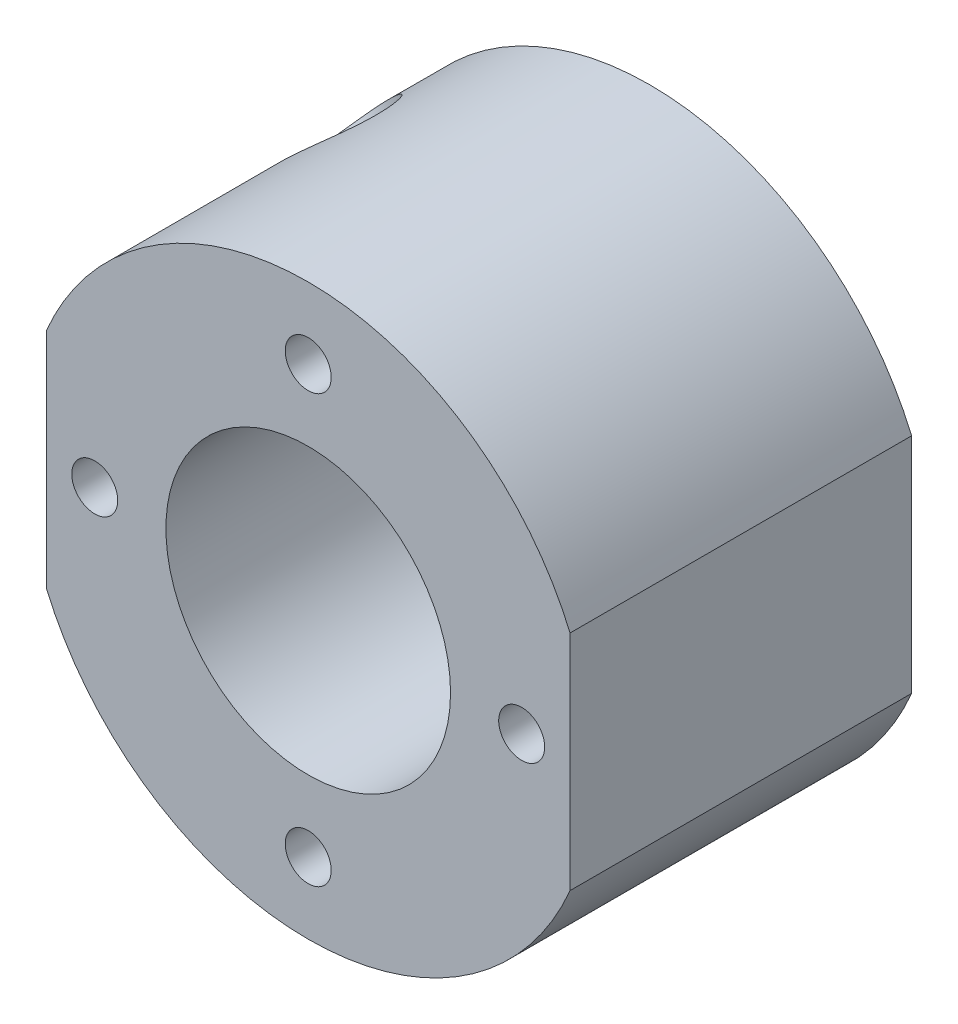
SolidWorks part; units mm, degrees
ref_plane "Front Plane" through (0, 0, 0) normal (0, 0, 1) x (1, 0, 0)
ref_plane "Top Plane" through (0, 0, 0) normal (0, 1, 0) x (1, 0, 0)
ref_plane "Right Plane" through (0, 0, 0) normal (1, 0, 0) x (0, 0, -1)
sketch "Sketch2" plane through (0, 0, 0) normal (0, 0, 1) x (1, 0, 0)
  line L0 (-23, 9.798) -> (-23, -9.798)
  line L1 (23, 9.798) -> (23, -9.798)
  line L2 (-23, 0) -> (23, 0) construction
  arc A0 (-23, -9.798) -> (23, -9.798) centre (0, 0) ccw
  arc A1 (23, 9.798) -> (-23, 9.798) centre (0, 0) ccw
  arc A2 (-23, 9.798) -> (-23, -9.798) centre (0, 0) ccw construction
  arc A3 (23, 9.798) -> (23, -9.798) centre (0, 0) cw construction
  point P10 (0, 0)
  dimension "D1" = 50
  dimension "D2" = 46
extrude "Boss-Extrude1" add sketch "Sketch2" along normal blind 30
sketch "Sketch6" plane through (0, 0, 30) normal (0, 0, 1) x (-1, 0, 0)
  circle A0 centre (0, 0) radius 12.5
  dimension "D1" = 25
extrude "Cut-Extrude1" cut sketch "Sketch6" against normal blind 25
hole_wizard "#10-32 Tapped Hole1" positions "Sketch9" profile "Sketch10" tap size "#10-32" standard "ANSI Inch" end condition through all
sketch "Sketch9" plane through (0, 0, 30) normal (0, 0, 1) x (1, 0, 0)
  line L0 (-18.75, 0) -> (18.75, 0) construction
  line L2 (0, 18.75) -> (0, -18.75) construction
  point P0 (-18.75, 0)
  point P2 (0, 18.75)
  point P4 (18.75, 0)
  point P6 (0, -18.75)
  dimension "D1" = 37.5
sketch "Sketch10" plane through (-18.75, 0, 30) normal (1, 0, 0) x (0, -1, 0)
  line L0 (0, 0) -> (0, 30)
  line L1 (0, 30) -> (2.0193, 30)
  line L2 (2.0193, 30) -> (2.0193, 0)
  line L5 (2.0193, 0) -> (0, 0)
  line L11 (0, -6.35) -> (0, 107.95) construction
  dimension "Thru Tap Drill Dia." = 4.0386
  dimension "Thru Tap Drill Depth" = 30
cosmetic thread "Hole Thread1" parameters "D2"=4.826
cosmetic thread "Hole Thread2" parameters "D2"=4.826
cosmetic thread "Hole Thread3" parameters "D2"=4.826
cosmetic thread "Hole Thread4" parameters "D2"=4.826
hole_wizard "1/8 NPT Tapped Hole1" positions "3DSketch4" profile "Sketch11" size "1/8" standard "ANSI Inch" end condition up to next
sketch3d "3DSketch4"
  line L0 (0, 0, 0) -> (-17.6777, 17.6777, 0) construction
  line L1 (-17.6777, 17.6777, 0) -> (-17.6777, 17.6777, 10) construction
  line L3 (0, 0, 0) -> (0, 0.8442, 0) construction
  arc A0 (23, 9.798, 0) -> (-23, 9.798, 0) centre (0, 0, 0) ccw construction
  point P0 (-17.6777, 17.6777, 10)
  point P12 (0, 0, 25)
  dimension "D1" = 45
  dimension "D2" = 10
sketch "Sketch11" plane through (-17.6777, 17.6777, 10) normal (0, 0, 1) x (-0.7071, -0.7071, 0)
  line L0 (0, 0) -> (0, 12.5)
  line L1 (0, 12.5) -> (4.2164, 12.5)
  line L2 (-4.5374, 6.92) -> (-4.7446, 0) construction
  line L3 (4.2164, 12.5) -> (4.2164, 6.92)
  line L4 (4.2164, 6.92) -> (4.5374, 6.92)
  line L5 (4.5374, 6.92) -> (4.7446, 0)
  line L7 (4.7446, 0) -> (0, 0)
  line L8 (0, -6.35) -> (0, 107.95) construction
  line L11 (-4.2164, 6.92) -> (-4.5374, 6.92) construction
  dimension "Thru Tap Drill Dia." = 8.4328
  dimension "Thru Tap Drill Depth" = 12.5
  dimension "Thread Dia." = 9.4892
  dimension "Thread Angle" = 3.43
  dimension "Thread Depth" = 6.92
cosmetic thread "Hole Thread5" parameters "D1"=6.92, "D2"=10.2867
